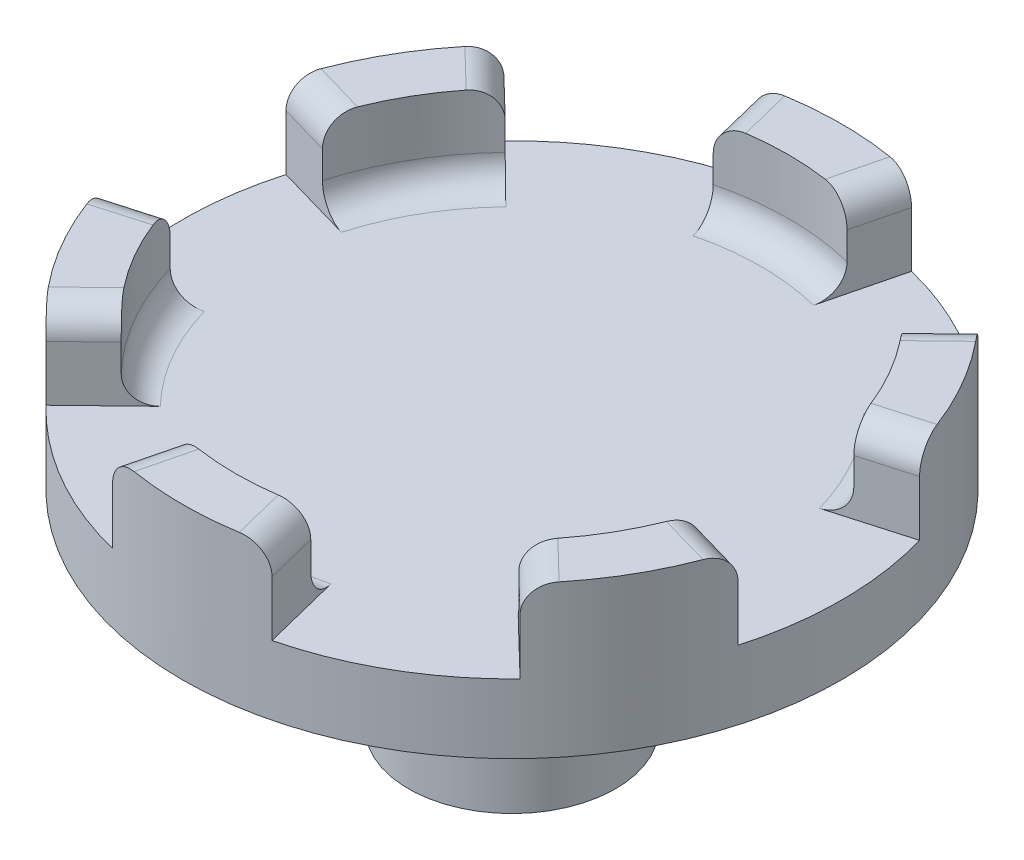
SolidWorks part; units mm, degrees
ref_plane "Front Plane" through (0, 0, 0) normal (0, 0, 1) x (1, 0, 0)
ref_plane "Top Plane" through (0, 0, 0) normal (0, 1, 0) x (1, 0, 0)
ref_plane "Right Plane" through (0, 0, 0) normal (1, 0, 0) x (0, 0, -1)
sketch "Sketch1" plane through (0, 0, 0) normal (0, 1, 0) x (1, 0, 0)
  circle A0 centre (0, 0) radius 30.2895
  dimension "D1" = 60.579
extrude "Boss-Extrude1" add sketch "Sketch1" along normal blind 6.35
sketch "Sketch2" plane through (0, 6.35, 0) normal (0, 1, 0) x (1, 0, 0)
  line L0 (-6.1482, -24.6447) -> (-7.3317, -29.3888)
  line L1 (-20.3643, -26.1375) -> (5.7009, -32.64) construction
  line L2 (-16.2324, -22.129) -> (3.936, -27.1604) construction
  line L3 (6.1482, -24.6447) -> (7.3317, -29.3888)
  line L4 (4.3414, -25.0954) -> (7.9549, -24.194) construction
  line L5 (8.1027, -29.1964) -> (6.5606, -29.5811) construction
  line L6 (-6.1482, -24.6447) -> (6.1482, -24.6447) construction
  line L7 (0, 0) -> (0, -49.2894) construction
  line L8 (-37.5524, 0) -> (37.5524, 0) construction
  line L9 (-24.417, -6.9979) -> (-29.1173, -8.345)
  line L10 (-18.2688, -17.6468) -> (-21.7856, -21.0438)
  line L11 (-18.2688, 17.6468) -> (-21.7856, 21.0438)
  line L12 (-24.417, 6.9979) -> (-29.1173, 8.345)
  line L13 (6.1482, 24.6447) -> (7.3317, 29.3888)
  line L14 (-6.1482, 24.6447) -> (-7.3317, 29.3888)
  line L15 (24.417, 6.9979) -> (29.1173, 8.345)
  line L16 (18.2688, 17.6468) -> (21.7856, 21.0438)
  line L17 (18.2688, -17.6468) -> (21.7856, -21.0438)
  line L18 (24.417, -6.9979) -> (29.1173, -8.345)
  line L19 (0, 0) -> (-6.1482, -24.6447) construction
  line L20 (0, 0) -> (-24.417, -6.9979) construction
  circle A0 centre (0, 0) radius 25.4 construction
  arc A1 (-18.2688, -17.6468) -> (-24.417, -6.9979) centre (0, 0) cw
  arc A2 (-21.7856, -21.0438) -> (-29.1173, -8.345) centre (0, 0) cw
  circle A3 centre (0, 0) radius 30.2895 construction
  arc A4 (6.1482, -24.6447) -> (-6.1482, -24.6447) centre (0, 0) cw
  arc A5 (7.3317, -29.3888) -> (-7.3317, -29.3888) centre (0, 0) cw
  arc A6 (-24.417, 6.9979) -> (-18.2688, 17.6468) centre (0, 0) cw
  arc A7 (-29.1173, 8.345) -> (-21.7856, 21.0438) centre (0, 0) cw
  arc A8 (-6.1482, 24.6447) -> (6.1482, 24.6447) centre (0, 0) cw
  arc A9 (-7.3317, 29.3888) -> (7.3317, 29.3888) centre (0, 0) cw
  arc A10 (18.2688, 17.6468) -> (24.417, 6.9979) centre (0, 0) cw
  arc A11 (21.7856, 21.0438) -> (29.1173, 8.345) centre (0, 0) cw
  arc A12 (24.417, -6.9979) -> (18.2688, -17.6468) centre (0, 0) cw
  arc A13 (29.1173, -8.345) -> (21.7856, -21.0438) centre (0, 0) cw
  point P10 (-7.3317, -29.3888)
  point P13 (-6.1482, -24.6447)
  point P18 (6.1482, -24.6447)
  point P20 (7.3317, -29.3888)
  point P23 (0, -24.6447)
  point P28 (0, 0)
  circle M16 centre (0, 0) radius 30.2895
  dimension "D1" = 50.8
  dimension "D2" = 6
  dimension "D3" = 60
extrude "Boss-Extrude2" add sketch "Sketch2" along normal blind 7.62 contours L3 A4 L0 M16 | L18 A12 L17 M16 | L16 A10 L15 M16 | L12 A6 L11 M16 | L10 A1 L9 M16 | A9 L13 A8 L14 region at (0, 6.35, 27.639) region at (-23.9361, 6.35, 13.8195) region at (23.9361, 6.35, 13.8195) region at (-23.9361, 6.35, -13.8195) region at (23.9361, 6.35, -13.8195)
fillet "Fillet1" radius 2.54 12 edges at (26.7671, 13.97, 7.6714) (26.7671, 13.97, -7.6714) (20.0272, 13.97, -19.3453) (6.7399, 13.97, -27.0167) (-6.7399, 13.97, -27.0167) (-20.0272, 13.97, -19.3453) (-26.7671, 13.97, -7.6714) (-26.7671, 13.97, 7.6714) (-20.0272, 13.97, 19.3453) (-6.7399, 13.97, 27.0167) (20.0272, 13.97, 19.3453) (6.7399, 13.97, 27.0167)
sketch "Sketch3" plane through (0, 0, 0) normal (0, -1, 0) x (1, 0, 0)
  circle A0 centre (0, 0) radius 12.7
  dimension "D1" = 25.4
extrude "Boss-Extrude3" add sketch "Sketch3" along normal blind 6.35
fillet "Fillet2" radius 2.54 6 edges at (-21.997, 6.35, 12.7) (-21.997, 6.35, -12.7) (0, 6.35, -25.4) (21.997, 6.35, -12.7) (0, 6.35, 25.4) (21.997, 6.35, 12.7)
sketch "Sketch4" plane through (0, -6.35, 0) normal (0, -1, 0) x (1, 0, 0)
  circle A0 centre (0, 0) radius 9.525
  dimension "D1" = 19.05
extrude "Boss-Extrude4" add sketch "Sketch4" along normal blind 12.7
